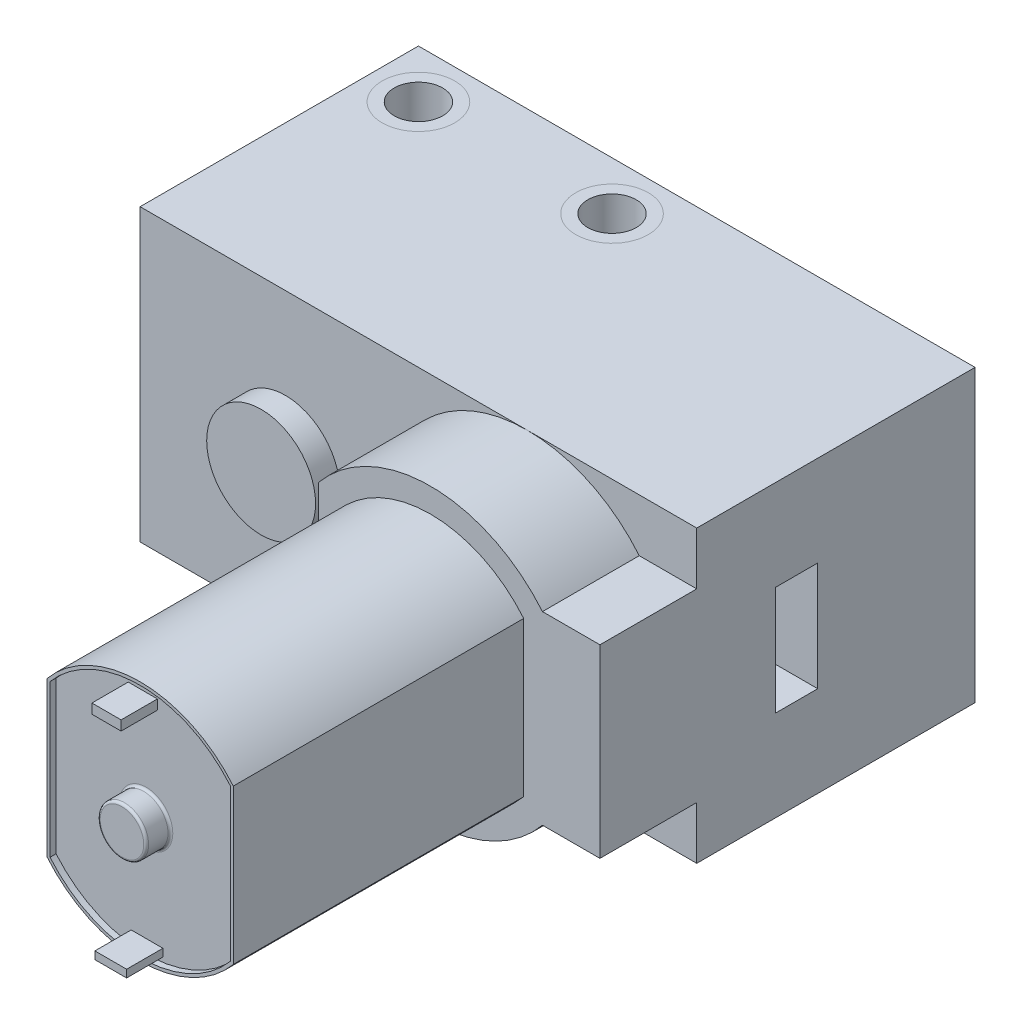
SolidWorks part; units mm, degrees
ref_plane "前视基准面" through (0, 0, 0) normal (0, 0, 1) x (1, 0, 0)
ref_plane "上视基准面" through (0, 0, 0) normal (0, 1, 0) x (1, 0, 0)
ref_plane "右视基准面" through (0, 0, 0) normal (1, 0, 0) x (0, 0, -1)
other "Configuration Table"
sketch "草图1" plane through (0, 0, 0) normal (0, 1, 0) x (1, 0, 0)
  line L1 (-23, -11.5) -> (23, -11.5)
  line L2 (-23, -11.5) -> (-23, 11.5)
  line L3 (-23, 11.5) -> (23, 11.5)
  line L4 (23, -11.5) -> (23, 11.5)
  line L5 (-23, -11.5) -> (23, 11.5) construction
  line L6 (-23, 11.5) -> (23, -11.5) construction
  point P0 (0, 0)
  dimension "D1" = 23
  dimension "D2" = 46
extrude "凸台-拉伸1" add sketch "草图1" along normal blind 24
sketch "草图2" plane through (0, 0, 11.5) normal (0, 0, 1) x (1, 0, 0)
  line L0 (-23, 0) -> (23, 0) construction
  line L1 (-23, 24) -> (23, 24) construction
  line L2 (23, 24) -> (23, 0) construction
  line L3 (-0.25, 19.6444) -> (-0.25, 4.3556)
  line L5 (9, 12) -> (9, 0) construction
  line L6 (18.25, 19.6444) -> (23, 19.6444)
  line L7 (18.25, 4.3556) -> (23, 4.3556)
  line L8 (23, 4.3556) -> (23, 19.6444)
  line L9 (9, 12) -> (23, 12) construction
  arc A0 (-0.25, 4.3556) -> (18.25, 4.3556) centre (9, 12) ccw
  arc A1 (18.25, 19.6444) -> (-0.25, 19.6444) centre (9, 12) ccw
  dimension "D1" = 14
  dimension "D2" = 9.25
  dimension "D3" = 15.2889
extrude "凸台-拉伸2" add sketch "草图2" along normal blind 8
sketch "草图3" plane through (0, 0, 19.5) normal (0, 0, 1) x (1, 0, 0)
  line L0 (1.3, 18.3804) -> (1.3, 5.6196)
  line L1 (16.7, 18.3804) -> (16.7, 5.6196)
  arc A0 (16.7, 18.3804) -> (1.3, 18.3804) centre (9, 12) ccw
  arc A1 (18.25, 19.6444) -> (9, 24) centre (9, 12) ccw construction
  arc A2 (1.3, 5.6196) -> (16.7, 5.6196) centre (9, 12) ccw
  dimension "D1" = 20
  dimension "D2" = 15.4
  dimension "D3" = 7.7
extrude "凸台-拉伸3" add sketch "草图3" along normal blind 24
sketch "草图4" plane through (0, 0, 11.5) normal (0, 0, 1) x (1, 0, 0)
  line L1 (-23, 24) -> (-23, 0) construction
  line L2 (-0.25, 19.6444) -> (-0.25, 4.3556) construction
  circle A0 centre (-11, 12) radius 4.5
  circle A1 centre (-0.25, 12) radius 2
  point P2 (-23, 12)
  dimension "D3" = 9
  dimension "D4" = 4
  dimension "D1" = 24
  dimension "D2" = 12
extrude "凸台-拉伸4" add sketch "草图4" along normal blind 2
sketch "草图6" plane through (23, 0, 0) normal (1, 0, 0) x (0, 0, -1)
  line L0 (11.5, 24) -> (11.5, 0) construction
  line L1 (-5, 16.5) -> (-1.5, 16.5)
  line L2 (-5, 16.5) -> (-5, 7.5)
  line L3 (-5, 7.5) -> (-1.5, 7.5)
  line L4 (-1.5, 16.5) -> (-1.5, 7.5)
  line L5 (-5, 16.5) -> (-1.5, 7.5) construction
  line L6 (-5, 7.5) -> (-1.5, 16.5) construction
  line L7 (-19.5, 4.3556) -> (-19.5, 19.6444) construction
  point P4 (-3.25, 12)
  point P5 (11.5, 12)
  dimension "D1" = 13
  dimension "D2" = 14.5
  dimension "D3" = 9
  dimension "D4" = 3.5
extrude "切除-拉伸1" cut sketch "草图6" against normal blind 5
sketch "草图7" plane through (0, 0, -11.5) normal (0, 0, -1) x (-1, 0, 0)
  circle A0 centre (11, 12) radius 2.7
  circle A1 centre (11, 12) radius 4.5 construction
  dimension "D1" = 5.4
extrude "凸台-拉伸5" add sketch "草图7" along normal blind 2
sketch "草图8" plane through (0, 0, -13.5) normal (0, 0, -1) x (-1, 0, 0)
  line L0 (9.25, 14.0561) -> (9.25, 9.9439)
  line L1 (12.75, 14.0561) -> (12.75, 9.9439)
  circle A0 centre (11, 12) radius 2.7 construction
  arc A1 (9.25, 9.9439) -> (12.75, 9.9439) centre (11, 12) ccw
  arc A2 (12.75, 14.0561) -> (9.25, 14.0561) centre (11, 12) ccw
  point P4 (11, 12)
  dimension "D1" = 3.5
  dimension "D2" = 1.75
extrude "凸台-拉伸6" add sketch "草图8" along normal blind 7
sketch "草图9" plane through (0, 0, -20.5) normal (0, 0, -1) x (-1, 0, 0)
  circle A0 centre (11, 12) radius 1.25
  dimension "D1" = 2.5
extrude "切除-拉伸2" cut sketch "草图9" against normal blind 5
sketch "草图10" plane through (0, 24, 0) normal (0, 1, 0) x (1, 0, 0)
  line L0 (23, 11.5) -> (-23, 11.5) construction
  line L1 (-23, 11.5) -> (-23, -11.5) construction
  circle A0 centre (-19, 7.5) radius 3
  circle A1 centre (-3, 7.5) radius 3
  dimension "D5" = 6
  dimension "D1" = 16
  dimension "D2" = 4
  dimension "D3" = 4
extrude "切除-拉伸3" cut sketch "草图10" against normal blind 8
extrude "切除-拉伸4" cut sketch "草图10<2>" along normal blind 8 from surface starting at face at (1.8, 0, 2.3)
sketch "草图10<2>" plane through (0, 24, 0) normal (0, 1, 0) x (1, 0, 0) same geometry as "草图10"
sketch "草图11" plane through (0, 0, -11.5) normal (0, 0, -1) x (-1, 0, 0)
  line L0 (12.75, 12) -> (-23, 12) construction
  line L1 (12.75, 9.9439) -> (12.75, 14.0561) construction
  line L2 (-23, 24) -> (-23, 0) construction
  circle A0 centre (-13, 20) radius 2
  circle A1 centre (-13, 4) radius 2
  dimension "D1" = 4
  dimension "D2" = 10
  dimension "D3" = 16
extrude "切除-拉伸5" cut sketch "草图11" against normal blind 8
sketch "Sketch1" plane through (0, 24, 0) normal (0, 1, 0) x (1, 0, 0)
  circle A0 centre (-19, 7.5) radius 2
  circle A1 centre (-3, 7.5) radius 2
  circle A2 centre (-3, 7.5) radius 3 construction
  circle A3 centre (-19, 7.5) radius 3 construction
  circle A4 centre (-3, 7.5) radius 3
  circle A5 centre (-19, 7.5) radius 3
  circle M1 centre (-19, 7.5) radius 3
  circle M2 centre (-3, 7.5) radius 3
  dimension "D1" = 4
  dimension "D2" = 4
extrude "Boss-Extrude1" add sketch "Sketch1" against normal up to surface (8 mm away) separate body up to face at (-19, 16, -4.5)
extrude "Boss-Extrude2" add sketch "Sketch1<2>" along direction (0, -1, 0) on the side of the normal up to surface (-16 mm away) from surface separate body contours A1 M2 | A0 M1 region at (-5.9151, 24, -7.5) region at (-21.9151, 24, -7.5) up to face at (-19, 8, -10.5) starting at face at (-19, 0, -10.5)
sketch "Sketch1<2>" plane through (0, 24, 0) normal (0, 1, 0) x (1, 0, 0) same geometry as "Sketch1"
sketch "Sketch2" plane through (0, 0, 43.5) normal (0, 0, 1) x (1, 0, 0)
  line L0 (16.45, 5.7103) -> (16.45, 18.2897)
  line L1 (1.55, 18.2897) -> (1.55, 5.7103)
  line L2 (16.7, 5.6196) -> (16.7, 18.3804)
  line L3 (1.3, 18.3804) -> (1.3, 5.6196)
  line L4 (16.7, 5.6196) -> (16.7, 18.3804) construction
  line L5 (1.3, 18.3804) -> (1.3, 5.6196) construction
  arc A0 (16.45, 18.2897) -> (1.55, 18.2897) centre (9, 12) ccw
  arc A1 (1.55, 5.7103) -> (16.45, 5.7103) centre (9, 12) ccw
  arc A2 (1.3, 5.6196) -> (16.7, 5.6196) centre (9, 12) ccw
  arc A3 (16.7, 18.3804) -> (1.3, 18.3804) centre (9, 12) ccw
  arc A4 (1.3, 5.6196) -> (16.7, 5.6196) centre (9, 12) ccw construction
  arc A5 (16.7, 18.3804) -> (1.3, 18.3804) centre (9, 12) ccw construction
  dimension "D1" = 0
  dimension "D2" = 0.25
extrude "Cut-Extrude1" cut sketch "Sketch2" against normal blind 0.5
sketch "Sketch3" plane through (0, 0, 43) normal (0, 0, 1) x (1, 0, 0)
  circle A0 centre (9, 12) radius 2
  dimension "D1" = 4
extrude "Boss-Extrude3" add sketch "Sketch3" along normal blind 2
fillet "Fillet1" radius 0.2 2 edges at (11, 12, 45) (11, 12, 43)
sketch "Sketch4" plane through (0, 0, 43) normal (0, 0, 1) x (1, 0, 0)
  line L1 (7.5159, 20.9841) -> (9.928, 20.9841)
  line L2 (7.5159, 20.9841) -> (7.5159, 20.1801)
  line L3 (7.5159, 20.1801) -> (9.928, 20.1801)
  line L4 (9.928, 20.9841) -> (9.928, 20.1801)
  line L5 (7.5159, 20.9841) -> (9.928, 20.1801) construction
  line L6 (7.5159, 20.1801) -> (9.928, 20.9841) construction
  line L7 (7.7606, 3.3655) -> (10.3824, 3.3655)
  line L8 (7.7606, 3.3655) -> (7.7606, 2.7362)
  line L9 (7.7606, 2.7362) -> (10.3824, 2.7362)
  line L10 (10.3824, 3.3655) -> (10.3824, 2.7362)
  line L11 (7.7606, 3.3655) -> (10.3824, 2.7362) construction
  line L12 (7.7606, 2.7362) -> (10.3824, 3.3655) construction
  point P4 (8.7219, 20.5821)
  point P9 (9.0715, 3.0508)
extrude "Boss-Extrude4" add sketch "Sketch4" along normal blind 3
equation "\"D3@草图3\"=\"D2@草图3\"/2"
equation "\"D2@草图4\"=\"D1@草图4\"/2"
